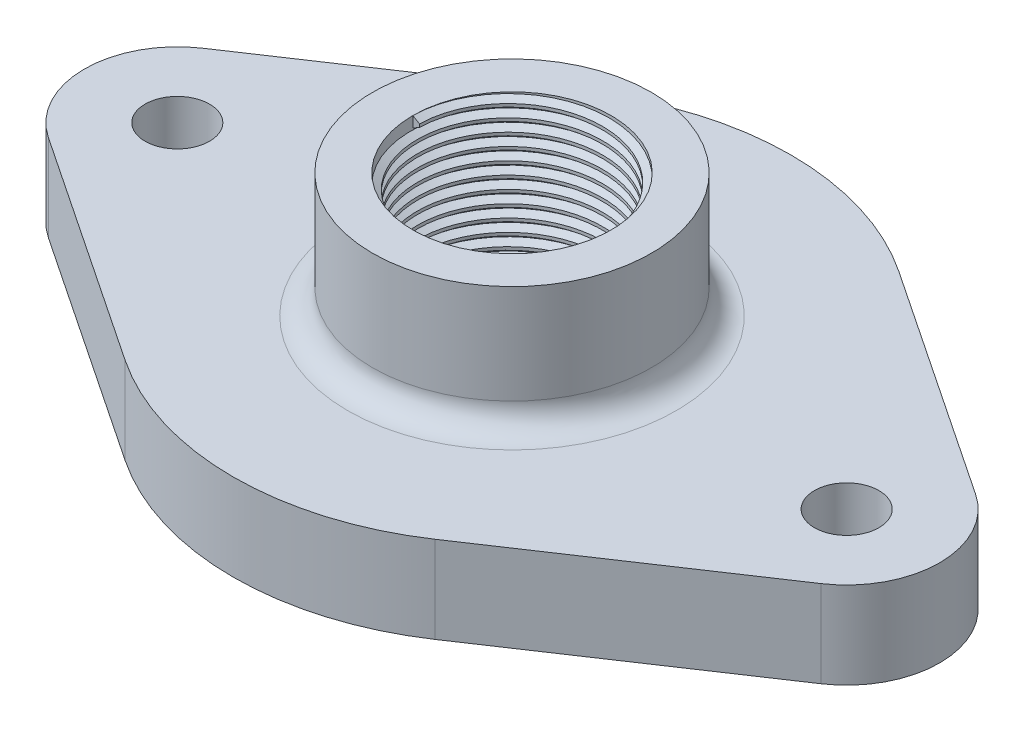
SolidWorks part; units mm, degrees
material "ABS"
ref_plane "Ön Düzlem" through (0, 0, 0) normal (0, 0, 1) x (1, 0, 0)
ref_plane "Üst Düzlem" through (0, 0, 0) normal (0, 1, 0) x (1, 0, 0)
ref_plane "Sağ Düzlem" through (0, 0, 0) normal (1, 0, 0) x (0, 0, -1)
sketch "Çizim1" plane through (0, 0, 0) normal (0, 1, 0) x (1, 0, 0)
  line L1 (-31.1667, 6.2361) -> (-12.5, 18.7083)
  line L2 (-31.1667, -6.2361) -> (-12.5, -18.7083)
  line L3 (12.5, 18.7083) -> (31.1667, 6.2361)
  line L4 (12.5, -18.7083) -> (31.1667, -6.2361)
  arc A0 (12.5, 18.7083) -> (-12.5, 18.7083) centre (0, 0) ccw
  arc A2 (-31.1667, 6.2361) -> (-31.1667, -6.2361) centre (-27, 0) ccw
  arc A3 (31.1667, -6.2361) -> (31.1667, 6.2361) centre (27, 0) ccw
  circle A4 centre (-27, 0) radius 2.6
  arc A5 (-12.5, -18.7083) -> (12.5, -18.7083) centre (0, 0) ccw
  circle A6 centre (27, 0) radius 2.6
  point P6 (0, 0)
  dimension "D1" = 22.5
  dimension "D2" = 7.5
  dimension "D4" = 5.2
  dimension "D5" = 5.2
  dimension "D3" = 54
extrude "Yükseklik-Ekstrüzyon1" add sketch "Çizim1" along normal blind 7
sketch "Çizim3" plane through (0, 7, 0) normal (0, 1, 0) x (1, 0, 0)
  circle A0 centre (0, 0) radius 11.25
  circle A1 centre (0, 0) radius 8
  dimension "D1" = 22.5
  dimension "D2" = 16
extrude "Yükseklik-Ekstrüzyon2" add sketch "Çizim3" along normal blind 10
sketch "Çizim4" plane through (0, 7, 0) normal (0, 1, 0) x (1, 0, 0)
  circle A0 centre (0, 0) radius 8
extrude "Kes-Ekstrüzyon1" cut sketch "Çizim4" against normal blind 5
thread "Diş1" pitch 1 method extrude profile "Diş Profili1" start angle 0, offset 0, length 0, pitch 1, diameter 16
ref_plane "Düzlem1" through (-8, 17, 0) normal (0, 0, 1) x (-1, 0, 0)
sketch "Diş Profili1" plane through (-8, 17, 0) normal (0, 0, 1) x (-1, 0, 0)
  line L0 (0, 0) -> (0, 1) construction
  line L11 (0, 0) -> (0, 0.875)
  line L12 (0, 0.875) -> (-0.5413, 0.5625)
  line L13 (-0.5413, 0.5625) -> (-0.5413, 0.3125)
  line L15 (-0.5413, 0.3125) -> (0, 0)
  line L17 (-0.5413, 0.4375) -> (0, 0.4375) construction
  point P2 (0, 0)
  dimension "Pitch" = 1
  dimension "Profile_Angle" = 60
  dimension "Profile_Land" = 0.25
  dimension "Profile_Height" = 0.5413
fillet "Radyus1" radius 2 1 edges at (0, 7, 11.25)
